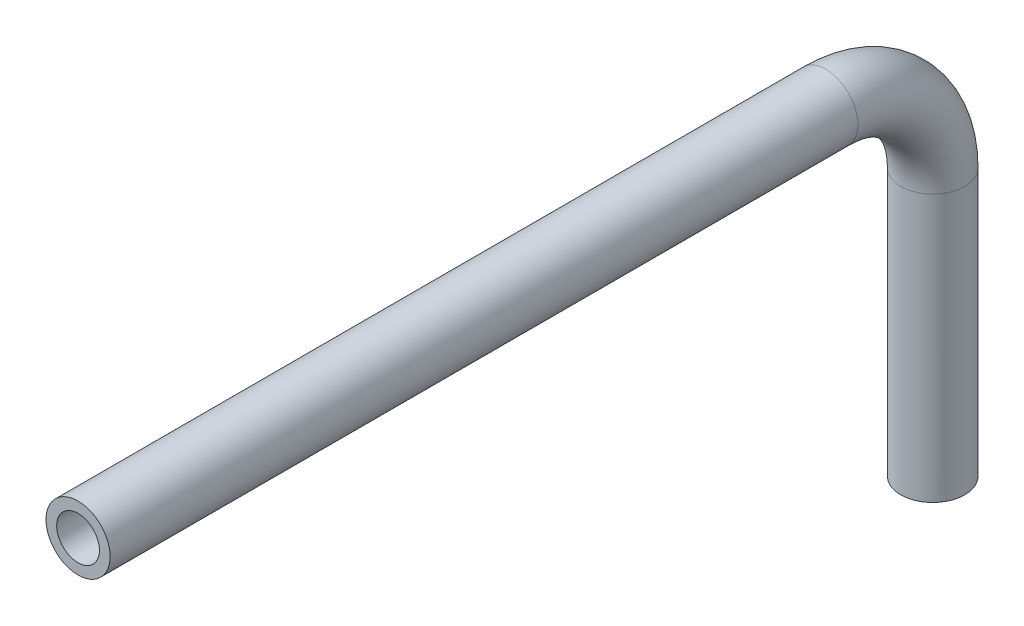
SolidWorks part; units mm, degrees
ref_plane "Front Plane" through (0, 0, 0) normal (0, 0, 1) x (1, 0, 0)
ref_plane "Top Plane" through (0, 0, 0) normal (0, 1, 0) x (1, 0, 0)
ref_plane "Right Plane" through (0, 0, 0) normal (1, 0, 0) x (0, 0, -1)
sketch "Sketch1" plane through (0, 0, 0) normal (1, 0, 0) x (0, 0, -1)
  line L0 (0, 0) -> (700, 0)
  line L1 (800, -100) -> (800, -350)
  arc A0 (700, 0) -> (800, -100) centre (700, -100) cw
  point P6 (800, 0)
  dimension "D3" = 100
  dimension "D1" = 800
  dimension "D2" = 350
sketch "Sketch2" plane through (0, 0, 0) normal (1, 0, 0) x (0, 0, -1)
sweep "Sweep-Thin1" add path "Sketch1" circular profile diameter 60 parameters "D1"=10, "D3"=60
